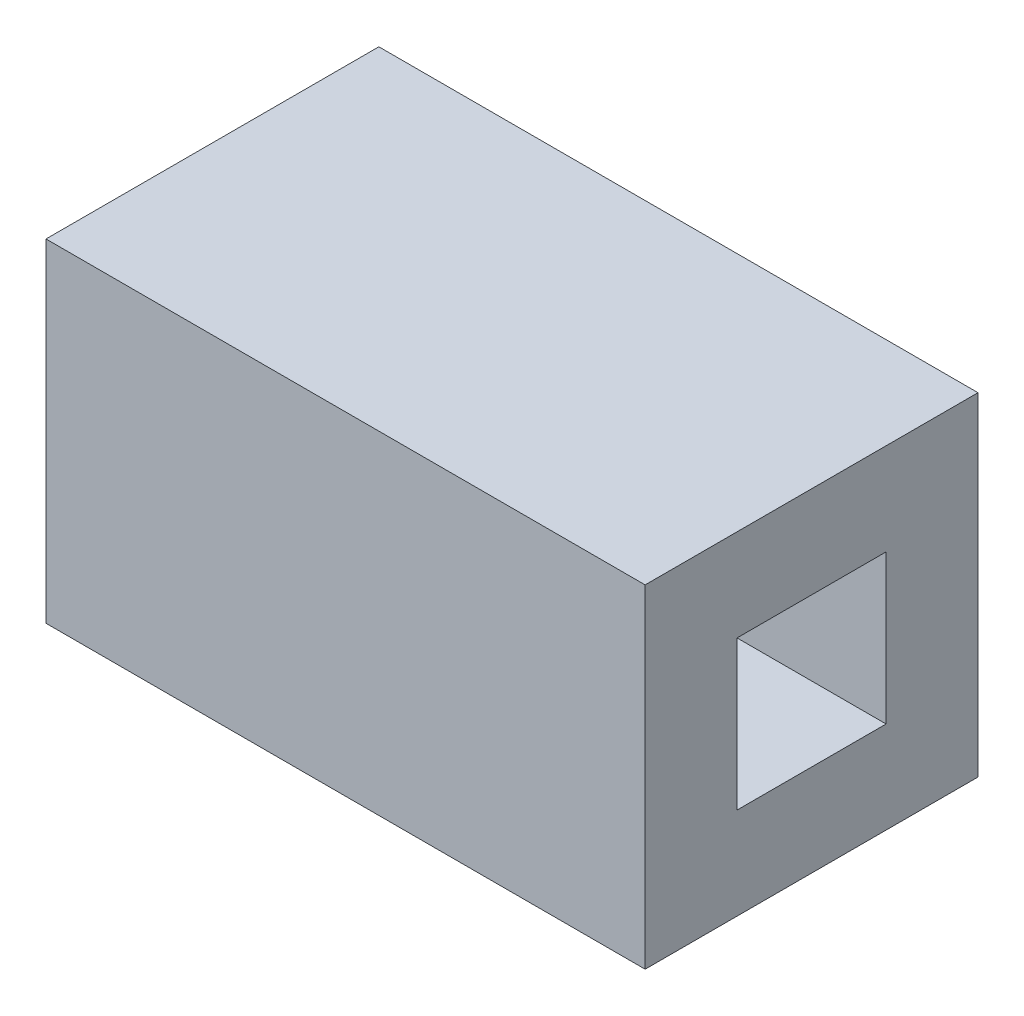
SolidWorks part; units mm, degrees
ref_plane "Alzado" through (0, 0, 0) normal (1, 0, 0) x (0, 1, 0)
ref_plane "Planta" through (0, 0, 0) normal (0, 0, 1) x (0, 1, 0)
ref_plane "Vista lateral" through (0, 0, 0) normal (0, 1, 0) x (-1, 0, 0)
sketch "Croquis1" plane through (0, 0, 0) normal (1, 0, 0) x (0, 1, 0)
  line L1 (-1.6794, -1.6794) -> (1.6794, -1.6794)
  line L2 (-1.6794, -1.6794) -> (-1.6794, 1.6794)
  line L3 (-1.6794, 1.6794) -> (1.6794, 1.6794)
  line L4 (1.6794, -1.6794) -> (1.6794, 1.6794)
  line L5 (-1.6794, -1.6794) -> (1.6794, 1.6794) construction
  line L6 (-1.6794, 1.6794) -> (1.6794, -1.6794) construction
  line L7 (-3.75, -3.75) -> (3.75, -3.75)
  line L8 (-3.75, -3.75) -> (-3.75, 3.75)
  line L9 (-3.75, 3.75) -> (3.75, 3.75)
  line L10 (3.75, -3.75) -> (3.75, 3.75)
  line L11 (-3.75, -3.75) -> (3.75, 3.75) construction
  line L12 (-3.75, 3.75) -> (3.75, -3.75) construction
  point P0 (0, 0)
  point P10 (0, 0)
  dimension "D1" = 7.5
  dimension "D2" = 4.75
extrude "Saliente-Extruir1" add sketch "Croquis1" against normal blind 7 contours L7 L10 L9 L8 L4 L1 L2 L3 | L1 L4 L3 L2 region at (0, 0, 0) region at (0, -3.6439, 0)
extrude "Saliente-Extruir2" add sketch "Croquis1<3>" along normal blind 6.5
sketch "Croquis1<3>" plane through (0, 0, 0) normal (1, 0, 0) x (0, 1, 0) same geometry as "Croquis1"
